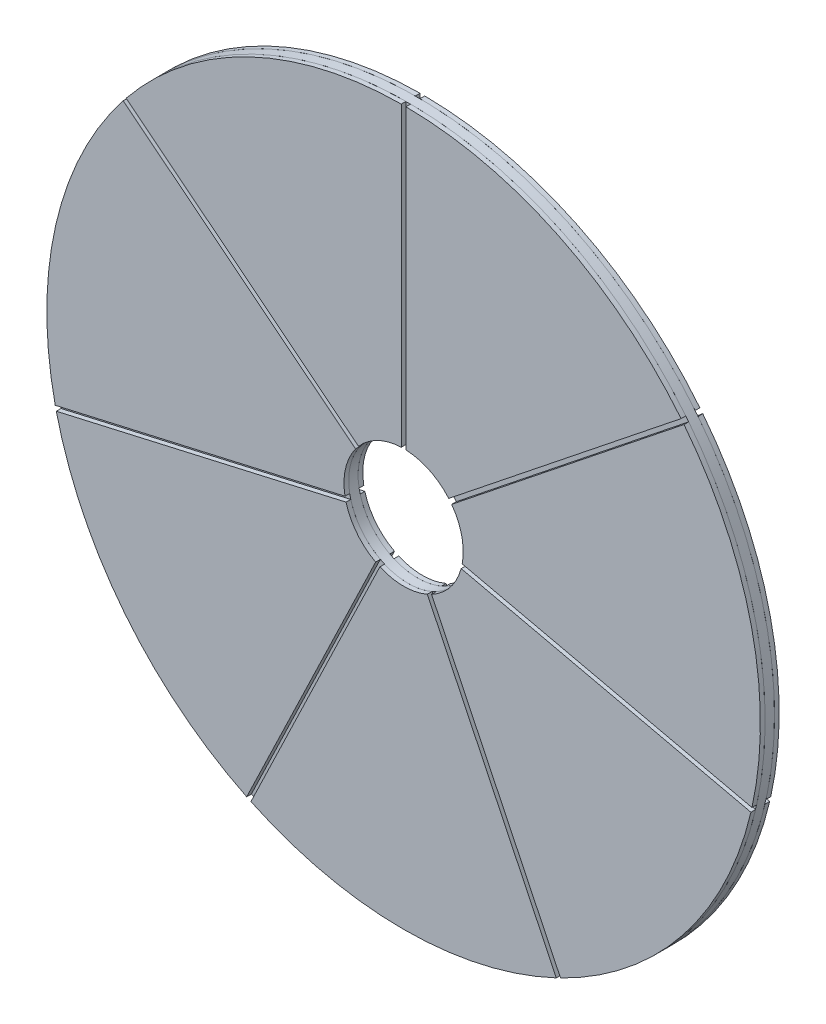
SolidWorks part; units mm, degrees
ref_plane "Front Plane" through (0, 0, 0) normal (0, 0, 1) x (1, 0, 0)
ref_plane "Top Plane" through (0, 0, 0) normal (0, 1, 0) x (1, 0, 0)
ref_plane "Right Plane" through (0, 0, 0) normal (1, 0, 0) x (0, 0, -1)
sketch "Sketch1" plane through (0, 0, 0) normal (0, 0, 1) x (1, 0, 0)
  circle A0 centre (0, 0) radius 19
  dimension "D1" = 38
extrude "Boss-Extrude1" add sketch "Sketch1" along normal blind 0.25 and the other way blind 0.25 contours A0
sketch "Sketch2" plane through (0, 0, 0.25) normal (0, 0, 1) x (1, 0, 0)
  line L0 (-0.0779, 0.0977) -> (0.0779, -0.0977)
  line L1 (-0.125, 0) -> (0.125, 0)
  line L2 (-0.125, 0) -> (-0.125, 19.4123)
  line L3 (-0.125, 19.4123) -> (0.125, 19.4123)
  line L4 (0.125, 0) -> (0.125, 19.4123)
  line L5 (-0.0779, 0.0977) -> (15.0992, 12.2011)
  line L6 (15.0992, 12.2011) -> (15.255, 12.0056)
  line L7 (0.0779, -0.0977) -> (15.255, 12.0056)
  line L8 (0.0278, 0.1219) -> (-0.0278, -0.1219)
  line L9 (0.0278, 0.1219) -> (18.9534, -4.1978)
  line L10 (18.9534, -4.1978) -> (18.8977, -4.4415)
  line L11 (-0.0278, -0.1219) -> (18.8977, -4.4415)
  line L12 (0.1126, 0.0542) -> (-0.1126, -0.0542)
  line L13 (0.1126, 0.0542) -> (8.5353, -17.4356)
  line L14 (8.5353, -17.4356) -> (8.31, -17.5441)
  line L15 (-0.1126, -0.0542) -> (8.31, -17.5441)
  line L16 (0.1126, -0.0542) -> (-0.1126, 0.0542)
  line L17 (0.1126, -0.0542) -> (-8.31, -17.5441)
  line L18 (-8.31, -17.5441) -> (-8.5353, -17.4356)
  line L19 (-0.1126, 0.0542) -> (-8.5353, -17.4356)
  line L20 (0.0278, -0.1219) -> (-0.0278, 0.1219)
  line L21 (0.0278, -0.1219) -> (-18.8977, -4.4415)
  line L22 (-18.8977, -4.4415) -> (-18.9534, -4.1978)
  line L23 (-0.0278, 0.1219) -> (-18.9534, -4.1978)
  line L24 (-0.0779, -0.0977) -> (0.0779, 0.0977)
  line L25 (-0.0779, -0.0977) -> (-15.255, 12.0056)
  line L26 (-15.255, 12.0056) -> (-15.0992, 12.2011)
  line L27 (0.0779, 0.0977) -> (-15.0992, 12.2011)
  circle A0 centre (0, 0) radius 19
  point P7 (0, 0)
  point P8 (0, 19.5429)
  point P15 (0, 0)
  point P19 (0, 0)
  point P21 (0, 0)
  point P26 (0, 0)
  point P31 (0, 0)
  point P36 (0, 0)
  point P41 (0, 0)
  point P42 (0, 0)
  circle M1 centre (0, 0) radius 19
  dimension "D1" = 7
  dimension "D2" = 38
extrude "Boss-Extrude2" add sketch "Sketch2" along normal blind 0.25 separate body contours L4 L5 M1 | L27 L2 M1 | L23 L25 M1 | L19 L21 M1 | L15 L17 M1 | L11 L13 M1 | L7 L9 M1 region at (5.3601, 11.1303, 0.25) region at (-5.3601, 11.1303, 0.25) region at (-12.044, 2.749, 0.25) region at (12.044, 2.749, 0.25) region at (9.6585, -7.7024, 0.25) region at (0, -12.3537, 0.25) region at (-9.6585, -7.7024, 0.25)
mirror "Mirror5" about plane through (0, 0, 0) normal (0, 0, 1) of bodies 125 124 144 122 120 123 143 104 103 102 141
sketch "Sketch3" plane through (0, 0, 0) normal (0, 0, 1) x (1, 0, 0)
  circle A0 centre (0, 0) radius 3.175
  dimension "D1" = 6.35
extrude "Cut-Extrude2" cut sketch "Sketch3" against normal blind 10 and the other way blind 10 contours A0
